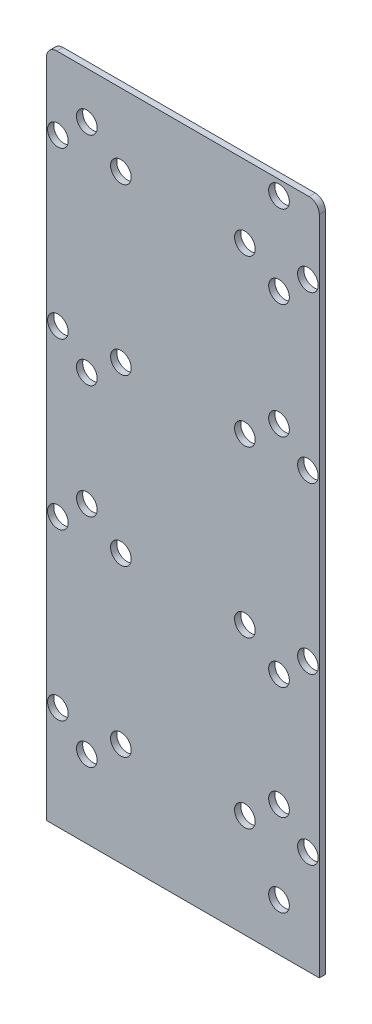
SolidWorks part; units mm, degrees
ref_plane "Front Plane" through (0, 0, 0) normal (0, 0, 1) x (1, 0, 0)
ref_plane "Top Plane" through (0, 0, 0) normal (0, 1, 0) x (1, 0, 0)
ref_plane "Right Plane" through (0, 0, 0) normal (1, 0, 0) x (0, 0, -1)
ref_plane "Plane4" through (0, 0, 3) normal (0, 0, 1) x (1, 0, 0)
sketch "Sketch1" plane through (0, 0, 3) normal (0, 0, 1) x (1, 0, 0)
  line L6 (-41.1488, 528.3974) -> (90.8512, 528.3974)
  line L7 (-41.1488, 528.3974) -> (-41.1488, 203.3974)
  line L8 (-41.1488, 203.3974) -> (90.8512, 203.3974)
  line L9 (90.8512, 528.3974) -> (90.8512, 203.3974)
  dimension "D1" = 325
  dimension "D2" = 132
extrude "Boss-Extrude1" add sketch "Sketch1" against normal blind 3
sketch "Sketch2" plane through (0, 0, 3) normal (0, 0, 1) x (1, 0, 0)
  line L0 (90.8512, 528.3974) -> (-41.1488, 528.3974) construction
  line L1 (90.8512, 203.3974) -> (90.8512, 528.3974) construction
  line L2 (-41.1488, 203.3974) -> (90.8512, 203.3974) construction
  circle A0 centre (71.3512, 521.3974) radius 5
  circle A1 centre (71.3512, 481.3974) radius 5
  circle A2 centre (71.3512, 425.8974) radius 5
  circle A3 centre (71.3512, 320.8974) radius 5
  circle A4 centre (71.3512, 266.3974) radius 5
  circle A5 centre (71.3512, 226.3974) radius 5
  dimension "D1" = 10
  dimension "D2" = 7
  dimension "D3" = 19.5
  dimension "D4" = 23
  dimension "D5" = 63
  dimension "D6" = 117.5
  dimension "D7" = 222.5
  dimension "D8" = 40
extrude "Cut-Extrude1" cut sketch "Sketch2" against normal through all
sketch "Sketch3" plane through (0, 0, 3) normal (0, 0, 1) x (1, 0, 0)
  line L0 (-41.1488, 203.3974) -> (90.8512, 203.3974) construction
  line L1 (-21.6488, 505.8974) -> (-21.6488, 400.8974) construction
  line L2 (-21.6488, 400.8974) -> (-21.6488, 345.8974) construction
  line L3 (-21.6488, 345.8974) -> (-21.6488, 240.8974) construction
  line L4 (-41.1488, 528.3974) -> (-41.1488, 203.3974) construction
  circle A0 centre (-21.6488, 505.8974) radius 5
  circle A1 centre (-21.6488, 400.8974) radius 5
  circle A2 centre (-21.6488, 345.8974) radius 5
  circle A3 centre (-21.6488, 240.8974) radius 5
  dimension "D5" = 10
  dimension "D1" = 37.5
  dimension "D2" = 142.5
  dimension "D3" = 197.5
  dimension "D4" = 302.5
  dimension "D6" = 19.5
extrude "Cut-Extrude2" cut sketch "Sketch3" against normal blind 10
sketch "Sketch4" plane through (0, 0, 3) normal (0, 0, 1) x (1, 0, 0)
  line L0 (85.3512, 253.3974) -> (54.8512, 253.3974) construction
  line L1 (54.8512, 253.3974) -> (-5.1488, 253.3974) construction
  line L2 (-5.1488, 253.3974) -> (-35.6488, 253.3974) construction
  line L3 (-41.1488, 203.3974) -> (90.8512, 203.3974) construction
  circle A0 centre (-35.6488, 253.3974) radius 5
  circle A1 centre (-5.1488, 253.3974) radius 5
  circle A2 centre (54.8512, 253.3974) radius 5
  circle A3 centre (85.3512, 253.3974) radius 5
  point P10 (24.8512, 253.3974)
  point P11 (24.8512, 203.3974)
  dimension "D1" = 10
  dimension "D2" = 30.5
  dimension "D3" = 30.5
  dimension "D4" = 60
  dimension "D5" = 50
extrude "Cut-Extrude3" cut sketch "Sketch4" against normal blind 10
pattern_linear "LPattern1" count 4 spacing 80 along (0, 1, 0) of "Cut-Extrude3"
fillet "Fillet1" radius 5 2 edges at (90.8512, 528.3974, 1.5) (-41.1488, 528.3974, 1.5)
